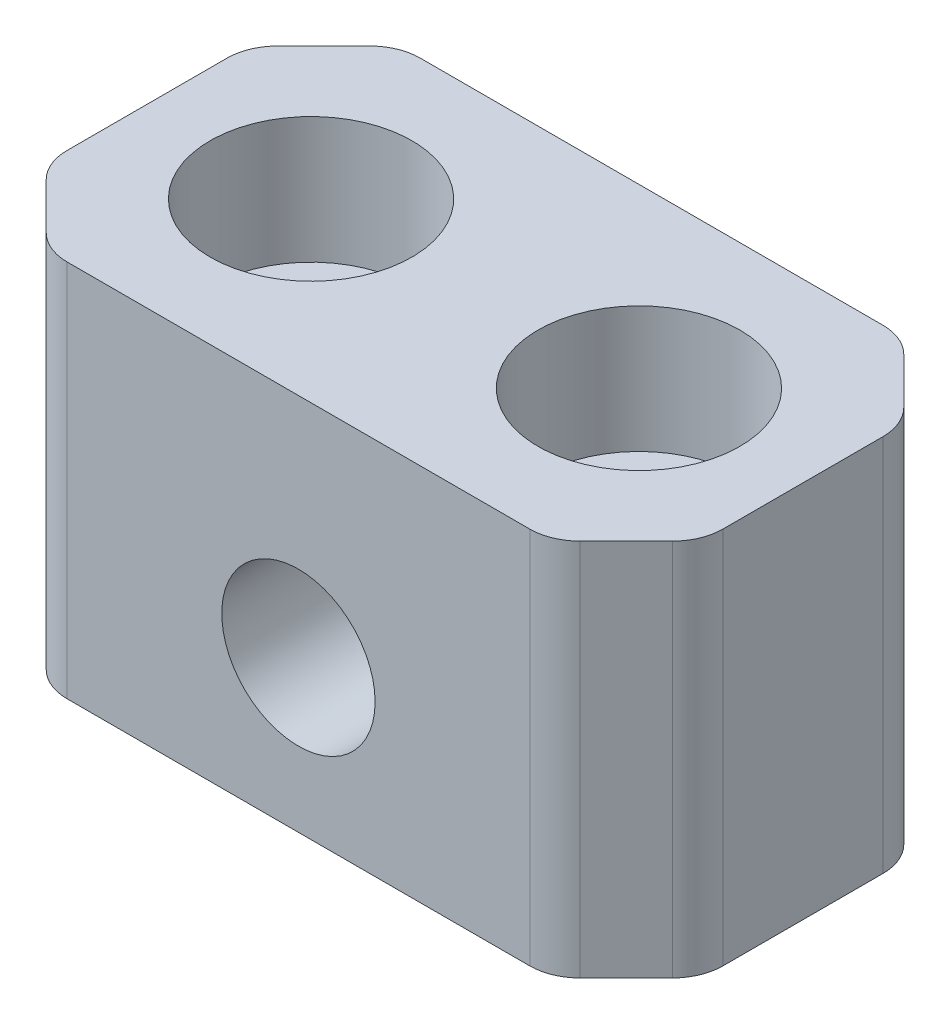
SolidWorks part; units mm, degrees
ref_plane "Front Plane" through (0, 0, 0) normal (0, 0, 1) x (1, 0, 0)
ref_plane "Top Plane" through (0, 0, 0) normal (0, 1, 0) x (1, 0, 0)
ref_plane "Right Plane" through (0, 0, 0) normal (1, 0, 0) x (0, 0, -1)
sketch "Sketch1" plane through (0, 0, 0) normal (0, 0, 1) x (1, 0, 0)
  line L1 (13, -7.5) -> (-13, -7.5)
  line L2 (13, -7.5) -> (13, 7.5)
  line L3 (13, 7.5) -> (-13, 7.5)
  line L4 (-13, -7.5) -> (-13, 7.5)
  line L5 (13, -7.5) -> (-13, 7.5) construction
  line L6 (13, 7.5) -> (-13, -7.5) construction
  point P0 (0, 0)
  dimension "D1" = 26
  dimension "D2" = 15
extrude "Boss-Extrude1" add sketch "Sketch1" along normal blind 7 and the other way blind 7
sketch "Sketch3" plane through (0, 0, 0) normal (0, 0, 1) x (1, 0, 0)
  line L0 (-13, -7.5) -> (13, -7.5) construction
  circle A0 centre (0, -1.5) radius 3.04
  dimension "D1" = 6.08
  dimension "D2" = 6
extrude "Cut-Extrude1" cut sketch "Sketch3" against normal blind 7 and the other way blind 7
sketch "Sketch4" plane through (0, 7.5, 0) normal (0, 1, 0) x (1, 0, 0)
  line L0 (0, 0) -> (0, -7) construction
  line L1 (-13, 7) -> (0, -7) construction
  line L2 (13, -7) -> (-13, -7) construction
  circle A0 centre (-6.5, 0) radius 4
  circle A1 centre (6.5, 0) radius 4
  dimension "D1" = 8
extrude "Cut-Extrude2" cut sketch "Sketch4" against normal blind 5
chamfer "Chamfer1" distance 3 angle 45 4 edges at (13, 0, -7) (13, 0, 7) (-13, 0, -7) (-13, 0, 7)
fillet "Fillet1" radius 2 8 edges at (-10, 0, -7) (-13, 0, -4) (10, 0, -7) (13, 0, -4) (13, 0, 4) (10, 0, 7) (-13, 0, 4) (-10, 0, 7)
sketch "Esquisse1" plane through (0, 2.5, 0) normal (0, 1, 0) x (1, 0, 0)
  circle A0 centre (6.5, 0) radius 2.75
  dimension "D1" = 5.5
extrude "Enlèv. mat.-Extru.1" cut sketch "Esquisse1" against normal blind 10
sketch "Esquisse2" plane through (0, 2.5, 0) normal (0, 1, 0) x (1, 0, 0)
  circle A0 centre (-6.5, 0) radius 2.75
  dimension "D1" = 5.5
extrude "Enlèv. mat.-Extru.2" cut sketch "Esquisse2" against normal blind 10
